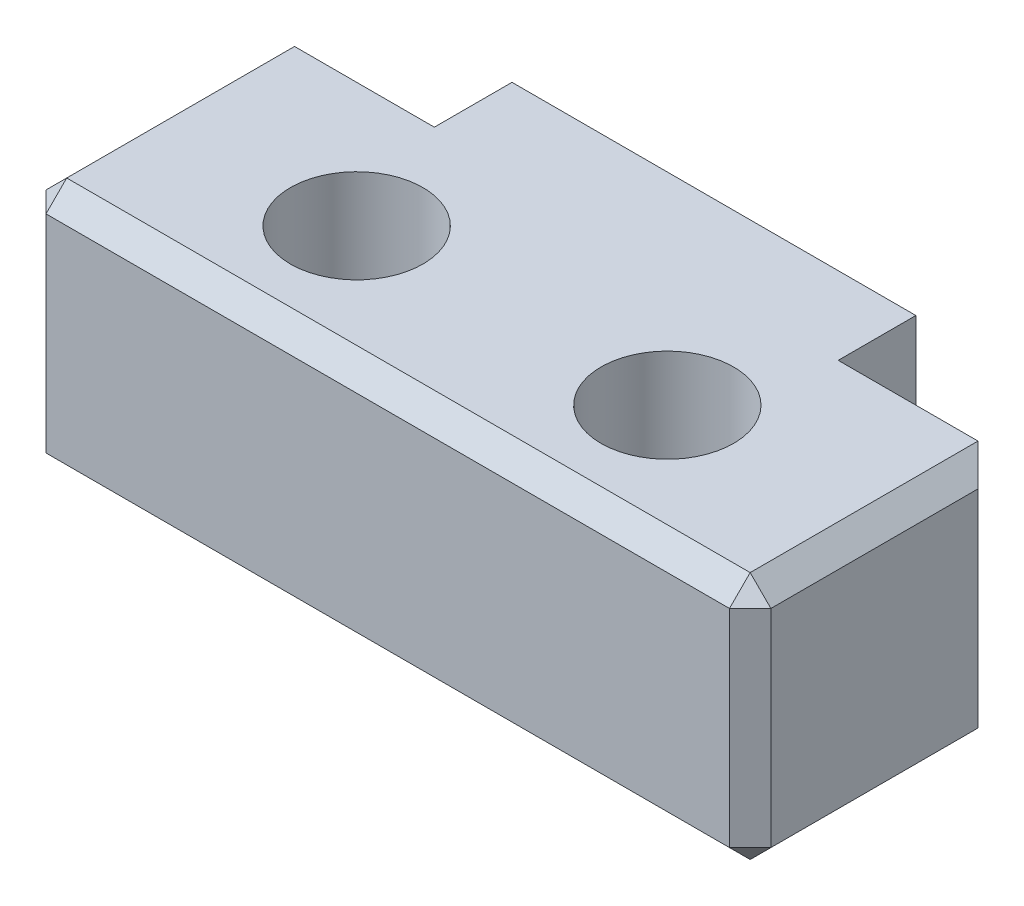
SolidWorks part; units mm, degrees
material "K110"
ref_plane "Front Plane" through (0, 0, 0) normal (0, 0, 1) x (1, 0, 0)
ref_plane "Top Plane" through (0, 0, 0) normal (0, 1, 0) x (1, 0, 0)
ref_plane "Right Plane" through (0, 0, 0) normal (1, 0, 0) x (0, 0, -1)
sketch "Sketch1" plane through (0, 0, 0) normal (0, 0, 1) x (1, 0, 0)
  line L1 (-17.5, -6) -> (17.5, -6)
  line L2 (-17.5, -6) -> (-17.5, 6)
  line L3 (-17.5, 6) -> (17.5, 6)
  line L4 (17.5, -6) -> (17.5, 6)
  line L5 (-17.5, -6) -> (17.5, 6) construction
  line L6 (-17.5, 6) -> (17.5, -6) construction
  point P0 (0, 0)
  dimension "D1" = 35
  dimension "D2" = 12
extrude "Boss-Extrude1" add sketch "Sketch1" along normal mid plane 12
sketch "Sketch3" plane through (0, 6, 0) normal (0, 1, 0) x (1, 0, 0)
  line L0 (17.5, 6) -> (-17.5, 6) construction
  line L1 (-9.75, 6) -> (9.75, 6)
  line L2 (-9.75, 6) -> (-9.75, 10.75)
  line L3 (-9.75, 10.75) -> (9.75, 10.75)
  line L4 (9.75, 6) -> (9.75, 10.75)
  point P6 (0, 6)
  dimension "D1" = 19.5
  dimension "D2" = 4.75
extrude "Boss-Extrude2" add sketch "Sketch3" against normal up to surface (12 mm away) up to face at (0, -6, 0)
sketch "Sketch4" plane through (0, 6, 0) normal (0, 1, 0) x (1, 0, 0)
  line L0 (0, -6) -> (0, 10.75) construction
  line L1 (17.5, -6) -> (-17.5, -6) construction
  line L2 (9.75, 10.75) -> (-9.75, 10.75) construction
  circle A0 centre (-7.5, 0) radius 5
  circle A1 centre (7.5, 0) radius 5
  point P4 (0, 0)
  dimension "D1" = 10
  dimension "D2" = 15
hole_wizard "M6 Clearance Hole1" positions "Sketch7" profile "Sketch6" hole size "M6" standard "ISO" end condition through all
sketch "Sketch7" plane through (0, 6, 0) normal (0, 1, 0) x (1, 0, 0)
  point P0 (-7.5, 0)
  point P3 (7.5, 0)
sketch "Sketch6" plane through (-7.5, 6, 0) normal (1, 0, 0) x (0, 0, 1)
  line L0 (0, 0) -> (0, 12)
  line L1 (0, 12) -> (3.2, 12)
  line L2 (3.2, 12) -> (3.2, 0)
  line L5 (3.2, 0) -> (0, 0)
  line L11 (0, -6.35) -> (0, 107.95) construction
  dimension "Thru Hole Dia." = 6.4
  dimension "Thru Hole Depth" = 12
chamfer "Chamfer4" distance 1 angle 45 14 edges at (0, -6, 6) (-17.5, 0, 6) (0, 6, 6) (17.5, 0, 6) (9.75, 0, -10.75) (0, 6, -10.75) (-9.75, 0, -10.75) (0, -6, -10.75) (-17.5, 6, 0) (-17.5, 0, -6) (-17.5, -6, 0) (17.5, -6, 0) (17.5, 0, -6) (17.5, 6, 0)
